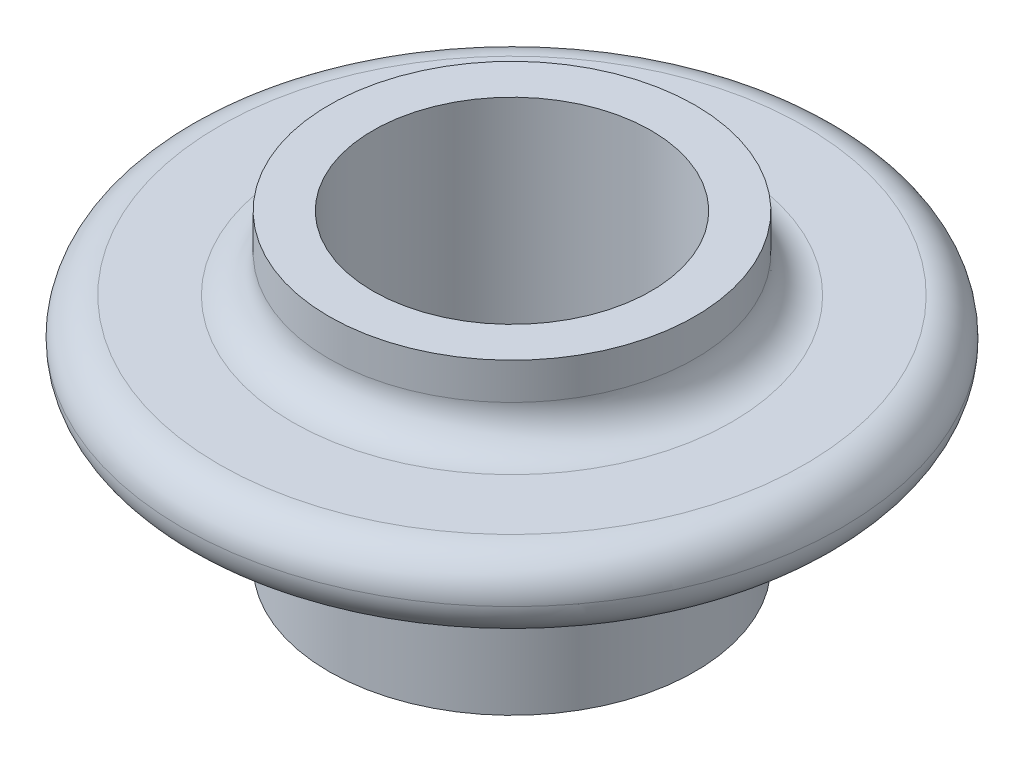
SolidWorks part; units mm, degrees
ref_plane "Front Plane" through (0, 0, 0) normal (0, 0, 1) x (1, 0, 0)
ref_plane "Top Plane" through (0, 0, 0) normal (0, 1, 0) x (1, 0, 0)
ref_plane "Right Plane" through (0, 0, 0) normal (1, 0, 0) x (0, 0, -1)
sketch "Sketch1" plane through (0, 0, 0) normal (0, 0, 1) x (1, 0, 0)
  line L0 (0, 0) -> (0, 32.1782) construction
  line L1 (19, 0) -> (19, 42)
  line L2 (19, 42) -> (25, 42)
  line L3 (25, 42) -> (25, 32)
  line L4 (25, 32) -> (45, 32)
  line L5 (45, 32) -> (45, 22)
  line L6 (45, 22) -> (25, 22)
  line L7 (25, 22) -> (25, 0)
  line L8 (25, 0) -> (19, 0)
  dimension "D1" = 10
  dimension "D2" = 42
  dimension "D3" = 10
  dimension "D4" = 19
  dimension "D5" = 25
  dimension "D6" = 45
revolve "Revolve1" add sketch "Sketch1" angle 360 about L0
fillet "Fillet1" radius 5 3 edges at (0, 32, -25) (0, 22, -45) (0, 32, -45)
